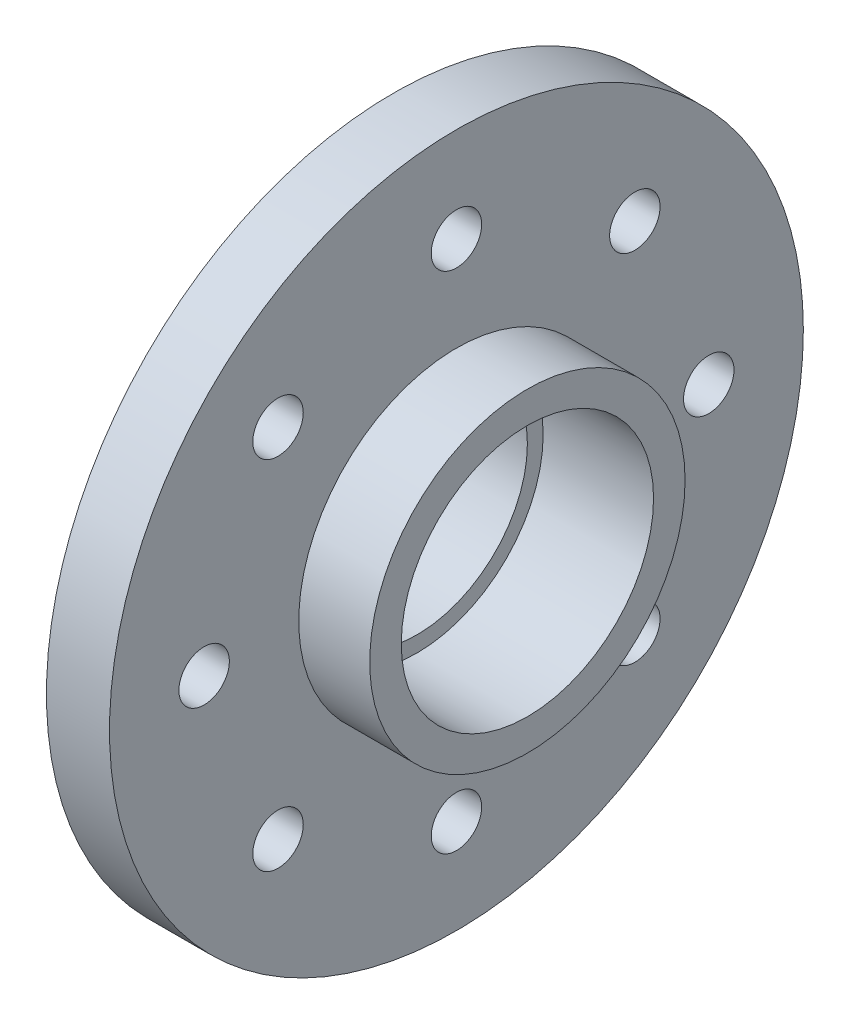
SolidWorks part; units mm, degrees
material "2024 Alloy (SN)"
ref_plane "Front Plane" through (0, 0, 0) normal (0, 0, 1) x (1, 0, 0)
ref_plane "Top Plane" through (0, 0, 0) normal (0, 1, 0) x (1, 0, 0)
ref_plane "Right Plane" through (0, 0, 0) normal (1, 0, 0) x (0, 0, -1)
sketch "Sketch1" plane through (0, 0, 0) normal (1, 0, 0) x (0, 0, -1)
  circle A0 centre (0, 0) radius 3.5
  circle A1 centre (0, 0) radius 5
  dimension "D1" = 7
  dimension "D2" = 10
extrude "Boss-Extrude1" add sketch "Sketch1" along normal blind 2
sketch "Sketch2" plane through (2, 0, 0) normal (1, 0, 0) x (0, 0, -1)
  circle A0 centre (0, 0) radius 4
  circle A1 centre (0, 0) radius 11
  dimension "D1" = 22
  dimension "D2" = 8
extrude "Boss-Extrude2" add sketch "Sketch2" along normal blind 1.25
extrude "Boss-Extrude3" add sketch "Sketch2<2>" against normal blind 0.75
sketch "Sketch2<2>" plane through (2, 0, 0) normal (1, 0, 0) x (0, 0, -1) same geometry as "Sketch2"
sketch "Sketch3" plane through (3.25, 0, 0) normal (1, 0, 0) x (0, 0, -1)
  circle A0 centre (0, 0) radius 4
  circle A1 centre (0, 0) radius 5
  dimension "D1" = 10
  dimension "D2" = 8
extrude "Boss-Extrude4" add sketch "Sketch3" along normal blind 2.25
sketch "Sketch4" plane through (3.25, 0, 0) normal (1, 0, 0) x (0, 0, -1)
  circle A0 centre (0, 0) radius 8
  circle A1 centre (0, 8) radius 1
  circle A2 centre (5.6569, 5.6569) radius 1
  circle A3 centre (8, 0) radius 1
  circle A4 centre (5.6569, -5.6569) radius 1
  circle A5 centre (0, -8) radius 1
  circle A6 centre (-5.6569, -5.6569) radius 1
  circle A7 centre (-8, 0) radius 1
  circle A8 centre (-5.6569, 5.6569) radius 1
  dimension "D1" = 16
  dimension "D2" = 2
  dimension "D3" = 8
hole_wizard "M2x0.4 Tapped Hole1" positions "Sketch6" profile "Sketch5" tap size "M2x0.4" standard "Ansi Metric"
sketch "Sketch6" plane through (3.25, 0, 0) normal (1, 0, 0) x (0, 0, -1)
  point P0 (8, 0)
  point P1 (0, 8)
  point P4 (-5.6569, 5.6569)
  point P7 (5.6569, 5.6569)
  point P10 (5.6569, -5.6569)
  point P13 (0, -8)
  point P16 (-5.6569, -5.6569)
  point P19 (-8, 0)
sketch "Sketch5" plane through (3.25, 0, -8) normal (0, 1, 0) x (0, 0, -1)
  line L0 (0, 0) -> (0, 5.6807)
  line L1 (0, 5.6807) -> (0.8, 5.2)
  line L2 (0.8, 5.2) -> (0.8, 0)
  line L5 (0.8, 0) -> (0, 0)
  line L10 (0, 5.6807) -> (-0.8, 5.2) construction
  line L11 (0, -6.35) -> (0, 107.95) construction
  dimension "Tap Drill Dia." = 1.6
  dimension "Tap Drill Depth" = 5.2
  dimension "Drill Angle" = 118
cosmetic thread "Hole Thread1" parameters "D1"=2, "D2"=2
cosmetic thread "Hole Thread2" parameters "D1"=2, "D2"=2
cosmetic thread "Hole Thread3" parameters "D1"=2, "D2"=2
cosmetic thread "Hole Thread4" parameters "D1"=2, "D2"=2
cosmetic thread "Hole Thread5" parameters "D1"=2, "D2"=2
cosmetic thread "Hole Thread6" parameters "D1"=2, "D2"=2
cosmetic thread "Hole Thread7" parameters "D1"=2, "D2"=2
cosmetic thread "Hole Thread8" parameters "D1"=2, "D2"=2
